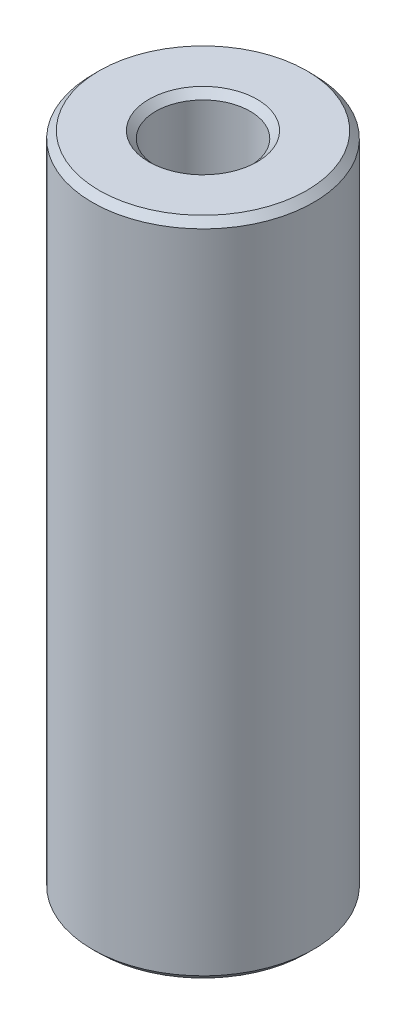
SolidWorks part; units mm, degrees
ref_plane "Front Plane" through (0, 0, 0) normal (0, 0, 1) x (1, 0, 0)
ref_plane "Top Plane" through (0, 0, 0) normal (0, 1, 0) x (1, 0, 0)
ref_plane "Right Plane" through (0, 0, 0) normal (1, 0, 0) x (0, 0, -1)
sketch "Sketch1" plane through (0, 0, 0) normal (0, 1, 0) x (1, 0, 0)
  circle A0 centre (0, 0) radius 52.5
  dimension "SLEEVE_OD" = 105
extrude "Boss-Extrude1" add sketch "Sketch1" along normal blind 313.6382
sketch "Sketch2" plane through (0, 0, 0) normal (0, 1, 0) x (1, 0, 0)
  circle A0 centre (0, 0) radius 22.4246
  dimension "BORE_D" = 44.8491
extrude "Cut-Extrude1" cut sketch "Sketch2" along normal through all
chamfer "Chamfer1" distance 3.3023 angle 44.527 4 edges at (0, 313.6382, 22.4246) (0, 0, 22.4246) (0, 0, 52.5) (0, 313.6382, 52.5) first distance on face at (0, 313.6382, 22.4246) first distance on face at (0, 0, 22.4246) first distance on face at (0, 313.6382, 52.5)
